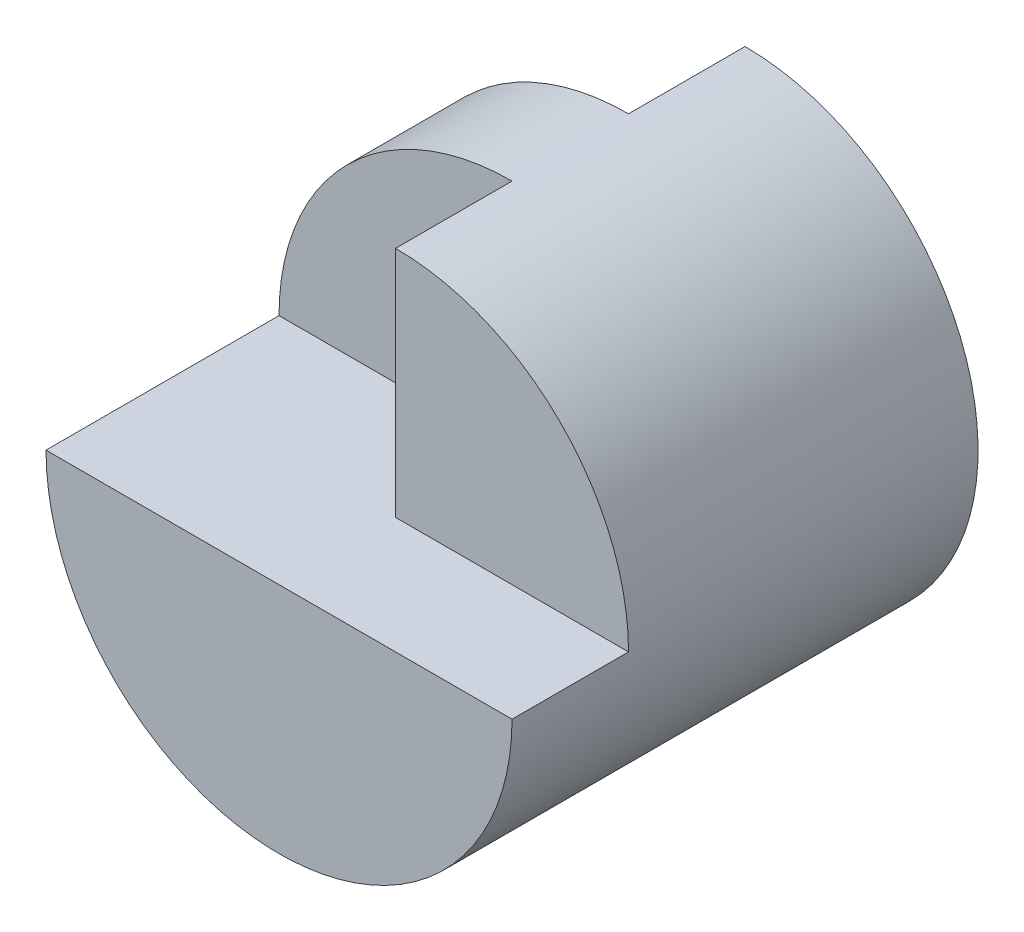
SolidWorks part; units mm, degrees
ref_plane "Front Plane" through (0, 0, 0) normal (0, 0, 1) x (1, 0, 0)
ref_plane "Top Plane" through (0, 0, 0) normal (0, 1, 0) x (1, 0, 0)
ref_plane "Right Plane" through (0, 0, 0) normal (1, 0, 0) x (0, 0, -1)
sketch "Sketch2" plane through (0, 0, 0) normal (0, 0, 1) x (1, 0, 0)
  circle A0 centre (0, 0) radius 20
  dimension "D1" = 40
extrude "Boss-Extrude1" add sketch "Sketch2" along normal blind 40
sketch "Sketch3" plane through (0, 0, 0) normal (1, 0, 0) x (0, 0, -1)
  line L1 (-40, 20) -> (-30, 20)
  line L2 (-40, 20) -> (-40, 0)
  line L3 (-40, 0) -> (-30, 0)
  line L4 (-30, 20) -> (-30, 0)
  dimension "D1" = 10
  dimension "D2" = 20
extrude "Cut-Extrude1" cut sketch "Sketch3" along normal blind 40 and the other way blind 40
sketch "Sketch4" plane through (0, 0, 30) normal (0, 0, 1) x (1, 0, 0)
  line L0 (0, 0) -> (0, 20)
  line L1 (-20, 0) -> (20, 0) construction
  line L2 (0, 0) -> (-20, 0)
  arc A0 (20, 0) -> (-20, 0) centre (0, 0) ccw construction
  arc A1 (0, 20) -> (-20, 0) centre (0, 0) ccw
  line M1 (-20, 0) -> (20, 0)
  arc M2 (20, 0) -> (-20, 0) centre (0, 0) ccw
extrude "Cut-Extrude2" cut sketch "Sketch4" against normal blind 10 contours L0 M1 M2 region at (-8.4883, 8.4883, 30)
sketch "Sketch5" plane through (0, 0, 0) normal (0, 0, -1) x (-1, 0, 0)
  line L0 (0, 20) -> (0, 0)
  line L1 (0, 0) -> (20, 0)
  arc A0 (0, 20) -> (20, 0) centre (0, 0) cw
  circle A1 centre (0, 0) radius 20 construction
extrude "Cut-Extrude3" cut sketch "Sketch5" against normal blind 10
